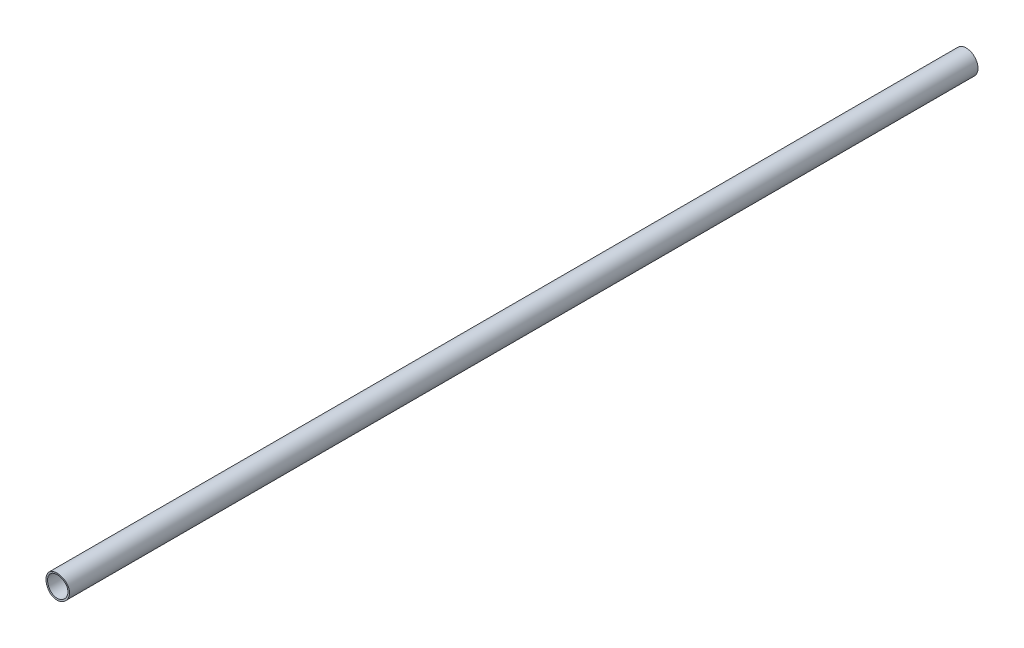
SolidWorks part; units mm, degrees
ref_plane "Front Plane" through (0, 0, 0) normal (0, 0, 1) x (1, 0, 0)
ref_plane "Top Plane" through (0, 0, 0) normal (0, 1, 0) x (1, 0, 0)
ref_plane "Right Plane" through (0, 0, 0) normal (1, 0, 0) x (0, 0, -1)
sketch "Sketch1" plane through (0, 0, 0) normal (0, 0, 1) x (1, 0, 0)
  circle A0 centre (0, 0) radius 19.05
  dimension "D1" = 38.1
extrude "Boss-Extrude1" add sketch "Sketch1" along normal blind 1524
shell "Shell1" thickness 2.54 removed face at (19.05, 0, 0)
sketch "Sketch2" plane through (0, 0, 0) normal (1, 0, 0) x (0, 0, -1)
  circle A0 centre (-1608.2835, 0) radius 136.0961
extrude "Cut-Extrude1" cut sketch "Sketch2" against normal blind 127 and the other way blind 127
ref_axis "Axis1" through (19.05, 0, 1608.2835) along (-1, 0, 0)
ref_axis "Axis2" through (0, 0, 1474.6154) along (0, 0, -1)
